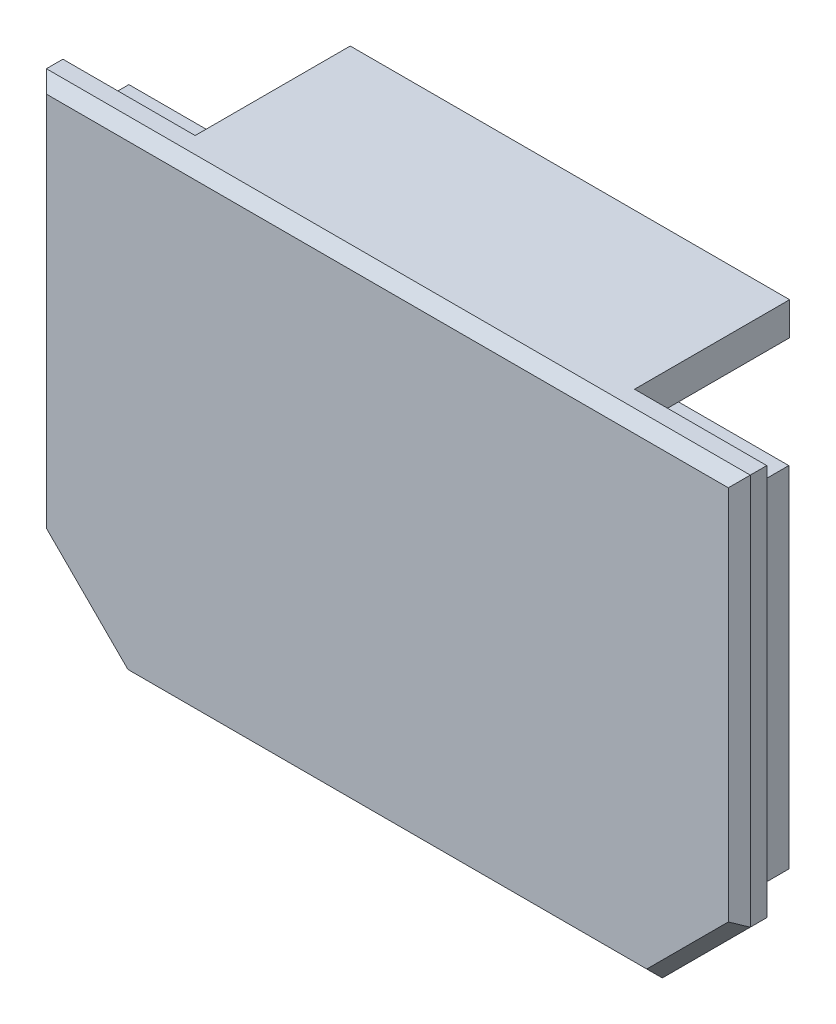
SolidWorks part; units mm, degrees
ref_plane "Front Plane" through (0, 0, 0) normal (0, 0, 1) x (1, 0, 0)
ref_plane "Top Plane" through (0, 0, 0) normal (0, 1, 0) x (1, 0, 0)
ref_plane "Right Plane" through (0, 0, 0) normal (1, 0, 0) x (0, 0, -1)
sketch "Sketch1" plane through (0, 0, 0) normal (0, 0, 1) x (1, 0, 0)
  line L32 (-20, -3) -> (-20, 0)
  line L33 (-20, 0) -> (-32, 0)
  line L34 (-32, 0) -> (-32, -35.6)
  line L35 (-32, -35.6) -> (-24, -43.6)
  line L36 (-24, -43.6) -> (24, -43.6)
  line L37 (24, -43.6) -> (32, -35.6)
  line L38 (32, -35.6) -> (32, 0)
  line L39 (32, 0) -> (20, 0)
  line L40 (20, 0) -> (20, -3)
  line L41 (20, -3) -> (30, -3)
  line L42 (30, -3) -> (30, -34.7716)
  line L43 (30, -34.7716) -> (23.1716, -41.6)
  line L44 (23.1716, -41.6) -> (-23.1716, -41.6)
  line L45 (-23.1716, -41.6) -> (-30, -34.7716)
  line L46 (-30, -34.7716) -> (-30, -3)
  line L47 (-30, -3) -> (-20, -3)
sketch "Sketch2" plane through (0, 0, 0) normal (0, 0, 1) x (1, 0, 0)
  line L0 (-30, -3) -> (30, -3) construction
  line L1 (30, -3) -> (30, -34.7716) construction
  line L2 (30, -34.7716) -> (23.1716, -41.6) construction
  line L3 (23.1716, -41.6) -> (-23.1716, -41.6) construction
  line L4 (-23.1716, -41.6) -> (-30, -34.7716) construction
  line L5 (-30, -34.7716) -> (-30, -3) construction
  line L6 (-28, -33.9431) -> (-28, -5)
  line L7 (-28, -5) -> (28, -5)
  line L8 (28, -5) -> (28, -33.9431)
  line L9 (28, -33.9431) -> (22.3431, -39.6)
  line L10 (22.3431, -39.6) -> (-22.3431, -39.6)
  line L11 (-22.3431, -39.6) -> (-28, -33.9431)
  line L12 (-29.9999, -3.0001) -> (29.9999, -3.0001)
  line L13 (29.9999, -3.0001) -> (29.9999, -34.7715)
  line L14 (29.9999, -34.7715) -> (23.1715, -41.5999)
  line L15 (23.1715, -41.5999) -> (-23.1715, -41.5999)
  line L16 (-23.1715, -41.5999) -> (-29.9999, -34.7715)
  line L17 (-29.9999, -34.7715) -> (-29.9999, -3.0001)
  dimension "D1" = 2
  dimension "D2" = 0.0001
extrude "Boss-Extrude1" add sketch "Sketch2" against normal blind 4
sketch "Sketch3" plane through (0, 0, 0) normal (0, 0, 1) x (1, 0, 0)
  line L0 (-32, 0) -> (32, 0)
  line L1 (32, 0) -> (32, -35.6)
  line L2 (32, -35.6) -> (24, -43.6)
  line L3 (24, -43.6) -> (-24, -43.6)
  line L4 (-24, -43.6) -> (-32, -35.6)
  line L5 (-32, -35.6) -> (-32, 0)
extrude "Boss-Extrude2" add sketch "Sketch3" along normal blind 2.5
chamfer "Chamfer1" distance 1 angle 45 6 edges at (0, 0, 2.5) (32, -17.8, 2.5) (28, -39.6, 2.5) (0, -43.6, 2.5) (-28, -39.6, 2.5) (-32, -17.8, 2.5)
sketch "Sketch4" plane through (0, -43.6, 0) normal (0, -1, 0) x (1, 0, 0)
  line L1 (-3, -0.75) -> (3, -0.75)
  line L2 (-3, -0.75) -> (-3, 0.75)
  line L3 (-3, 0.75) -> (3, 0.75)
  line L4 (3, -0.75) -> (3, 0.75)
  line L5 (-3, -0.75) -> (3, 0.75) construction
  line L6 (-3, 0.75) -> (3, -0.75) construction
  point P0 (0, 0)
  dimension "D1" = 6
  dimension "D2" = 1.5
extrude "Cut-Extrude1" cut sketch "Sketch4" against normal up to surface (2.0001 mm away) up to face at (0, -41.5999, -2)
chamfer "Chamfer2" distance 1 angle 45 2 edges at (3, -42.5999, 0.75) (-3, -42.5999, 0.75)
sketch "Sketch5" plane through (0, 0, 0) normal (0, 0, -1) x (-1, 0, 0)
  line L0 (-32, 0) -> (32, 0) construction
  line L1 (-19.975, 0) -> (19.975, 0)
  line L2 (-19.975, 0) -> (-19.975, -3.0001)
  line L3 (-19.975, -3.0001) -> (19.975, -3.0001)
  line L4 (19.975, 0) -> (19.975, -3.0001)
  line L5 (-29.9999, -3.0001) -> (29.9999, -3.0001) construction
  line L6 (-20, 0) -> (-20, -3) construction
  line L7 (20, -3) -> (20, 0) construction
  dimension "D1" = 0.025
  dimension "D2" = 0.025
extrude "Boss-Extrude3" add sketch "Sketch5" along normal blind 14.1
